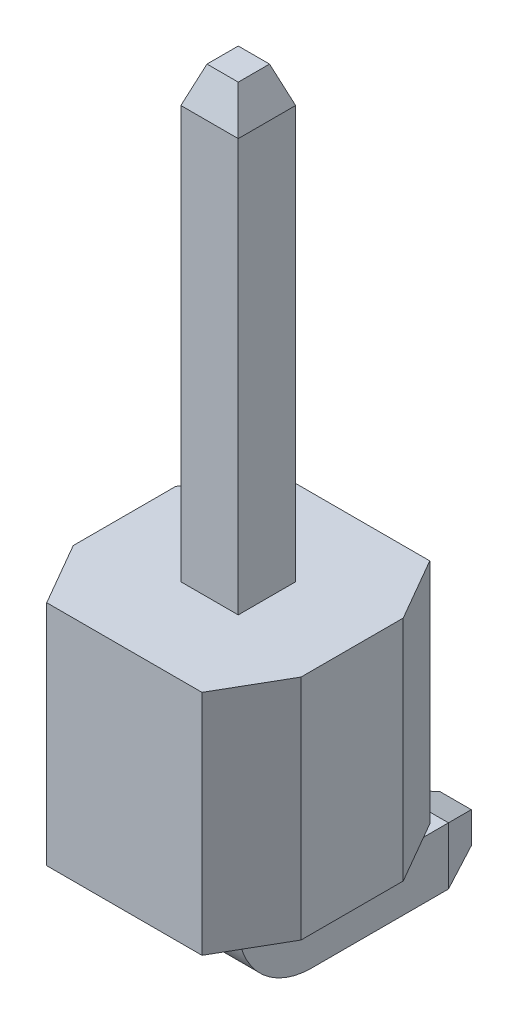
SolidWorks part; units mm, degrees
ref_plane "Front Plane" through (0, 0, 0) normal (0, 0, 1) x (1, 0, 0)
ref_plane "Top Plane" through (0, 0, 0) normal (0, 1, 0) x (1, 0, 0)
ref_plane "Right Plane" through (0, 0, 0) normal (1, 0, 0) x (0, 0, -1)
sketch "Sketch1" plane through (0, 0, 0) normal (1, 0, 0) x (0, 0, -1)
  line L0 (-2.4243, 3.1405) -> (-2.4243, -4.8595)
  line L1 (-1.9243, -5.3595) -> (0.1157, -5.3595)
  arc A0 (-2.4243, -4.8595) -> (-1.9243, -5.3595) centre (-1.9243, -4.8595) ccw
  point P5 (-2.4243, -5.3595)
  dimension "D3" = 0.5
  dimension "D1" = 8.5
  dimension "D2" = 2.54
sketch "Sketch2" plane through (0, 0, 0) normal (0, 0, 1) x (1, 0, 0)
  line L1 (0.32, -5.0395) -> (-0.32, -5.0395)
  line L2 (0.32, -5.0395) -> (0.32, -5.6795)
  line L3 (0.32, -5.6795) -> (-0.32, -5.6795)
  line L4 (-0.32, -5.0395) -> (-0.32, -5.6795)
  line L5 (0.32, -5.0395) -> (-0.32, -5.6795) construction
  line L6 (0.32, -5.6795) -> (-0.32, -5.0395) construction
  point P0 (0, -5.3595)
  dimension "D1" = 0.64
  dimension "D2" = 0.64
sweep "Sweep1" add profiles "Sketch2" path "Sketch1"
chamfer "Chamfer1" distance 0.4 angle 20 8 edges at (0, -5.6795, 0) (0.32, -5.3595, 0) (0, -5.0395, 0) (-0.32, -5.3595, 0) (0, 3.1405, 2.1043) (0.32, 3.1405, 2.4243) (0, 3.1405, 2.7443) (-0.32, 3.1405, 2.4243) tangent propagation no first distance on face at (0, -5.6795, 0.9621) first distance on face at (0.32, -3.1354, 1.7191) first distance on face at (0, -5.0395, 0.9621) first distance on face at (-0.32, -3.1354, 1.7191) first distance on face at (0, -0.8595, 2.1043) first distance on face at (0, -0.8595, 2.7443)
ref_plane "Plane1" through (0, -4.3995, 0) normal (0, 1, 0) x (-1, 0, 0)
sketch "Sketch5" plane through (0, -4.3995, 0) normal (0, 1, 0) x (-1, 0, 0)
  line L0 (0.1744, 2.2498) -> (-0.1744, 2.5987) construction
  line L1 (-0.1744, 2.5987) -> (0.1744, 2.5987) construction
  line L2 (0.1744, 2.5987) -> (-0.1744, 2.2498) construction
sketch "Sketch6" plane through (0, -4.3995, 0) normal (0, 1, 0) x (-1, 0, 0)
  line L0 (0.1744, 2.2498) -> (-0.1744, 2.5987) construction
  line L1 (-1.27, 1.1543) -> (1.27, 1.1543)
  line L2 (-1.27, 1.1543) -> (-1.27, 3.6943)
  line L3 (-1.27, 3.6943) -> (1.27, 3.6943)
  line L4 (1.27, 1.1543) -> (1.27, 3.6943)
  line L5 (-1.27, 1.1543) -> (1.27, 3.6943) construction
  line L6 (-1.27, 3.6943) -> (1.27, 1.1543) construction
  point P0 (0, 2.4243)
  dimension "D1" = 2.54
  dimension "D2" = 2.54
extrude "Extrude1" add sketch "Sketch6" along normal blind 2.54 separate body
chamfer "Chamfer2" distance 0.7 angle 30 4 edges at (-1.27, -3.1295, 3.6943) (-1.27, -3.1295, 1.1543) (1.27, -3.1295, 3.6943) (1.27, -3.1295, 1.1543) first distance on face at (-1.27, -3.1295, 2.4243) first distance on face at (1.27, -3.1295, 2.4243)
